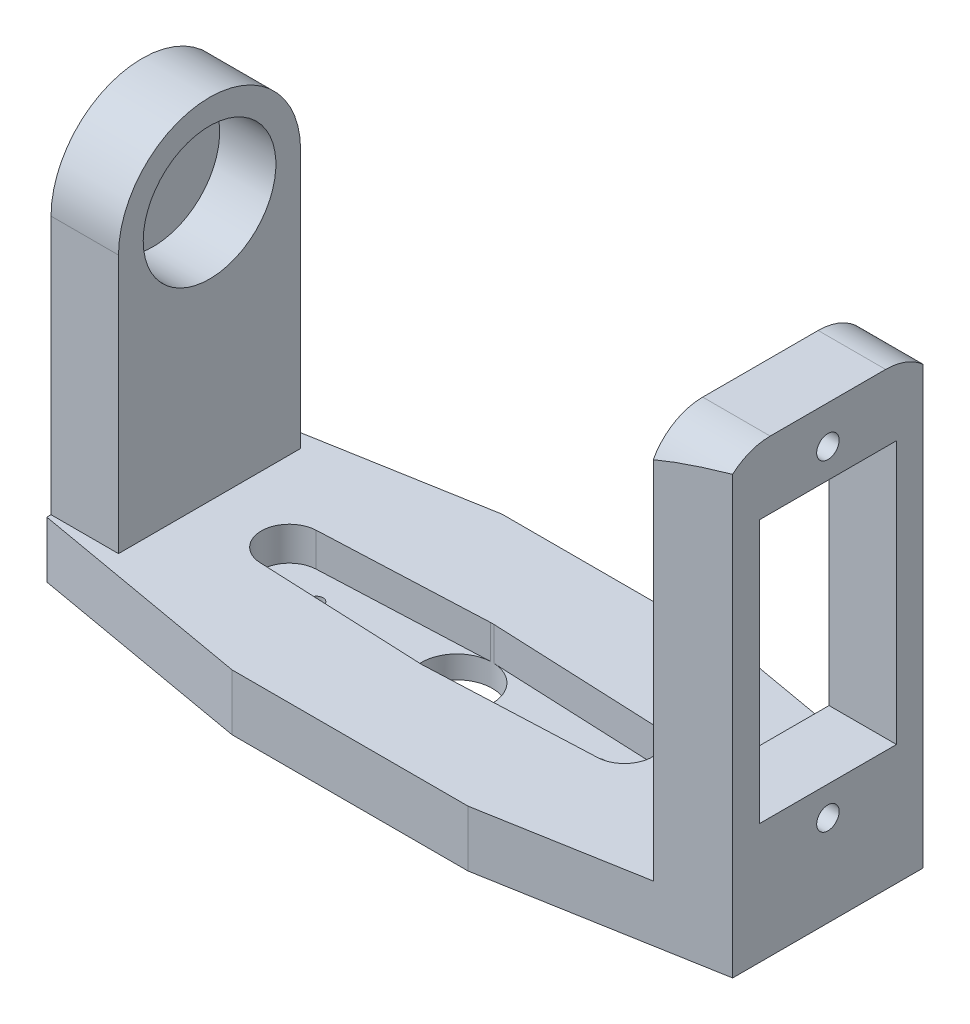
SolidWorks part; units mm, degrees
ref_plane "前视基准面" through (0, 0, 0) normal (0, 0, 1) x (1, 0, 0)
ref_plane "上视基准面" through (0, 0, 0) normal (0, 1, 0) x (1, 0, 0)
ref_plane "右视基准面" through (0, 0, 0) normal (1, 0, 0) x (0, 0, -1)
sketch "草图1" plane through (0, 0, 0) normal (0, 1, 0) x (1, 0, 0)
  line L0 (0, 0) -> (2.5, 0) construction
  line L1 (33, -12) -> (-28, -12)
  line L2 (33, -12) -> (33, 12)
  line L3 (33, 12) -> (-28, 12)
  line L4 (-28, -12) -> (-28, 12)
  line L5 (33, -12) -> (-28, 12) construction
  line L6 (33, 12) -> (-28, -12) construction
  point P0 (0, 0)
  dimension "D1" = 28
  dimension "D2" = 33
  dimension "D3" = 24
extrude "凸台-拉伸1" add sketch "草图1" along normal blind 5
sketch "草图2" plane through (-28, 0, 0) normal (-1, 0, 0) x (0, 0, 1)
  line L0 (-12, 5) -> (12, 5) construction
  line L1 (8.0991, 36.0991) -> (-8.0991, 36.0991)
  line L2 (8.0991, 36.0991) -> (8.0991, 5)
  line L3 (8.0991, 5) -> (-8.0991, 5)
  line L4 (-8.0991, 36.0991) -> (-8.0991, 5)
  line L5 (8.0991, 36.0991) -> (-8.0991, 5) construction
  line L6 (8.0991, 5) -> (-8.0991, 36.0991) construction
  line L7 (0, 20.5496) -> (0, 5) construction
  circle A0 centre (0, 28) radius 5.9
  circle A1 centre (0, 28) radius 8.0991 construction
  point P0 (0, 20.5496)
  dimension "D2" = 11.8
  dimension "D1" = 23
extrude "凸台-拉伸2" add sketch "草图2" against normal blind 6
sketch "草图8" plane through (-28, 0, 0) normal (-1, 0, 0) x (0, 0, 1)
  circle A1 centre (0, 28) radius 5.9 construction
  circle A2 centre (0, 28) radius 5.9
extrude "凸台-拉伸4" add sketch "草图8" against normal blind 1
fillet "圆角1" 2 edges at (-25, 36.0991, -8.0991) (-25, 36.0991, 8.0991) type full round first side face at (-25, 20.5496, -8.0991) second side face at (-25, 20.5496, 8.0991) middle face at (-25, 36.0991, 0)
sketch "草图3" plane through (33, 0, 0) normal (1, 0, 0) x (0, 0, -1)
  line L0 (0, 22.4) -> (18.2252, 22.4) construction
  line L1 (10.134, 40.0752) -> (-10.134, 40.0752)
  line L2 (10.134, 40.0752) -> (10.134, 5)
  line L3 (10.134, 5) -> (-10.134, 5)
  line L4 (-10.134, 40.0752) -> (-10.134, 5)
  line L5 (10.134, 40.0752) -> (-10.134, 5) construction
  line L6 (10.134, 5) -> (-10.134, 40.0752) construction
  line L7 (0, 22.4) -> (0, 0) construction
  line L8 (6.1, 34.1) -> (-6.1, 34.1)
  line L9 (6.1, 34.1) -> (6.1, 10.7)
  line L10 (6.1, 10.7) -> (-6.1, 10.7)
  line L11 (-6.1, 34.1) -> (-6.1, 10.7)
  line L12 (6.1, 34.1) -> (-6.1, 10.7) construction
  line L13 (6.1, 10.7) -> (-6.1, 34.1) construction
  line L17 (-12, 5) -> (12, 5) construction
  circle A0 centre (0, 28) radius 5.9 construction
  circle A1 centre (0, 28) radius 5.9 construction
  circle A2 centre (0, 8.1) radius 1
  circle A3 centre (0, 36.7) radius 1
  circle A4 centre (0, 28) radius 6.1 construction
  point P0 (0, 22.5376)
  point P7 (0, 22.4)
  dimension "D5" = 2
  dimension "D1" = 23.4
  dimension "D2" = 12.2
  dimension "D4" = 14.3
extrude "凸台-拉伸3" add sketch "草图3" against normal blind 6
fillet "圆角2" radius 5 2 edges at (30, 40.0752, 10.134) (30, 40.0752, -10.134)
sketch "草图4" plane through (-24, 5, 6) normal (0, -1, 0) x (-1, 0, 0)
  line L0 (-24, 6) -> (-9.0984, 6) construction
  line L1 (-8.998, 3.7022) -> (-23.8713, 3.0528) construction
  line L2 (-23.8713, 8.9472) -> (-8.998, 8.2978) construction
  line L3 (-23.8626, 9.147) -> (-8.9893, 8.4976)
  line L4 (-8.9893, 3.5024) -> (-23.8626, 2.853)
  arc A0 (-23.8713, 8.9472) -> (-23.8713, 3.0528) centre (-24, 6) ccw construction
  arc A1 (-8.998, 3.7022) -> (-8.998, 8.2978) centre (-9.0984, 6) ccw construction
  arc A2 (-8.9893, 3.5024) -> (-8.9893, 8.4976) centre (-9.0984, 6) ccw
  arc A3 (-23.8626, 9.147) -> (-23.8626, 2.853) centre (-24, 6) ccw
  dimension "D1" = 5.9
  dimension "D2" = 4.6
  dimension "D3" = 5
  dimension "D5" = 0.2
extrude "切除-拉伸1" cut sketch "草图4" along normal blind 3
mirror "镜向1" about plane through (0, 0, 0) normal (1, 0, 0) of "切除-拉伸1"
sketch "草图5" plane through (0, 2, 0) normal (0, 1, 0) x (1, 0, 0)
  line L0 (-12.5, 0) -> (0, 0) construction
  line L1 (0, 0) -> (0, 5.837) construction
  arc A1 (-0.1374, -3.147) -> (0.1374, -3.147) centre (0, 0) ccw construction
  arc A2 (0.1374, 3.147) -> (-0.1374, 3.147) centre (0, 0) ccw construction
  arc A3 (-0.1374, -3.147) -> (0.1374, -3.147) centre (0, 0) ccw construction
  arc A4 (0.1374, 3.147) -> (-0.1374, 3.147) centre (0, 0) ccw construction
  circle A5 centre (0, 0) radius 3.15
  circle A6 centre (-12.5, 0) radius 0.6
  circle A7 centre (12.5, 0) radius 0.6
  dimension "D2" = 1.2
  dimension "D1" = 12.5
extrude "切除-拉伸2" cut sketch "草图5" against normal blind 2.4
chamfer "倒角1" distance 20 angle 10 4 edges at (33, 2.5, -12) (33, 2.5, 12) (-28, 2.5, 12) (-28, 2.5, -12) first distance on face at (2.5, 2.5, -12) first distance on face at (2.5, 2.5, 12)
